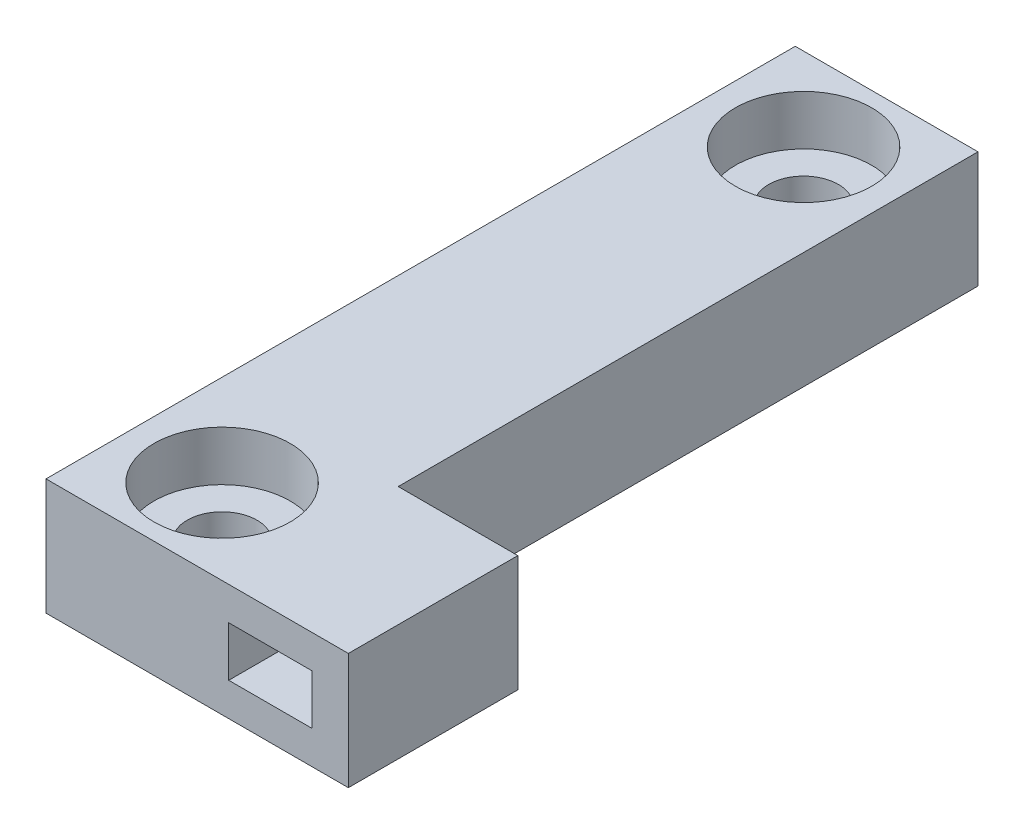
SolidWorks part; units mm, degrees
ref_plane "Front Plane" through (0, 0, 0) normal (0, 0, 1) x (1, 0, 0)
ref_plane "Top Plane" through (0, 0, 0) normal (0, 1, 0) x (1, 0, 0)
ref_plane "Right Plane" through (0, 0, 0) normal (1, 0, 0) x (0, 0, -1)
sketch "Sketch1" plane through (0, 0, 0) normal (0, 1, 0) x (1, 0, 0)
  line L0 (0, 0) -> (18.2, 0)
  line L1 (18.2, 0) -> (18.2, 10.2)
  line L2 (18.2, 10.2) -> (11, 10.2)
  line L3 (11, 10.2) -> (11, 45.1)
  line L4 (11, 45.1) -> (0, 45.1)
  line L5 (0, 45.1) -> (0, 0)
  dimension "D1" = 18.2
  dimension "D2" = 10.2
  dimension "D3" = 45.1
  dimension "D4" = 11
extrude "Boss-Extrude1" add sketch "Sketch1" along normal blind 7
sketch "Sketch2" plane through (0, 0, 0) normal (0, 0, 1) x (1, 0, 0)
  line L0 (18.2, 7) -> (18.2, 0) construction
  line L1 (11, 5) -> (16, 5)
  line L2 (11, 5) -> (11, 2)
  line L3 (11, 2) -> (16, 2)
  line L4 (16, 5) -> (16, 2)
  line L5 (11, 7) -> (0, 7) construction
  point P6 (18.2, 3.5)
  point P7 (16, 3.5)
  point P10 (13.5, 2)
  point P11 (5.5, 7)
  dimension "D1" = 8
  dimension "D2" = 5
  dimension "D3" = 3
extrude "Cut-Extrude1" cut sketch "Sketch2" against normal up to next contours L1 L4 L3 L2
sketch "Sketch3" plane through (0, 7, 0) normal (0, 1, 0) x (1, 0, 0)
  line L1 (11, 45.1) -> (0, 45.1) construction
  line L2 (18.2, 0) -> (18.2, 10.2) construction
  circle A0 centre (5.5, 5.1) radius 2.1
  circle A1 centre (5.5, 40.1) radius 2.1
  point P14 (5.5, 45.1)
  point P15 (18.2, 5.1)
  dimension "D1" = 4.2
  dimension "D2" = 35
  dimension "D3" = 4.2
extrude "Cut-Extrude2" cut sketch "Sketch3" against normal up to next contours A1 | A0 region at (5.5, 7, -40.1)
sketch "Sketch4" plane through (0, 7, 0) normal (0, 1, 0) x (1, 0, 0)
  circle A0 centre (5.5, 5.1) radius 4.1
  circle A1 centre (5.5, 40.1) radius 4.1
  dimension "D1" = 8.2
  dimension "D2" = 8.2
extrude "Cut-Extrude3" cut sketch "Sketch4" against normal blind 3
